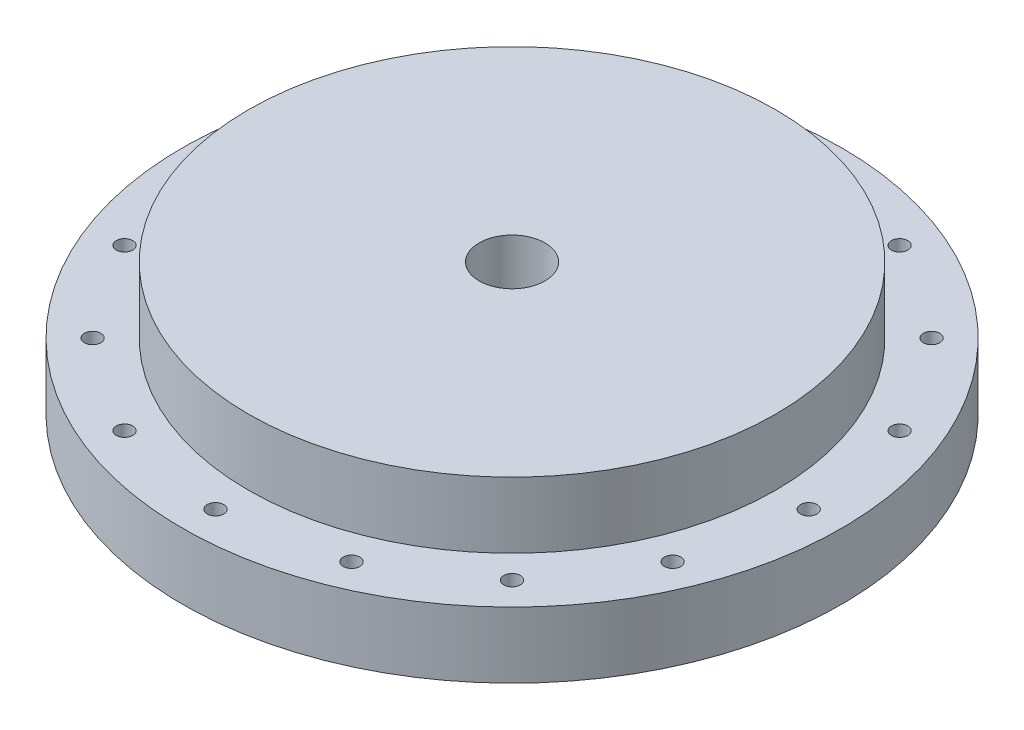
SolidWorks part; units mm, degrees
ref_plane "Front Plane" through (0, 0, 0) normal (0, 0, 1) x (1, 0, 0)
ref_plane "Top Plane" through (0, 0, 0) normal (0, 1, 0) x (1, 0, 0)
ref_plane "Right Plane" through (0, 0, 0) normal (1, 0, 0) x (0, 0, -1)
sketch "Sketch1" plane through (0, 0, 0) normal (0, 1, 0) x (1, 0, 0)
  circle A1 centre (0, 0) radius 50.8
  dimension "D1" = 101.6
extrude "Boss-Extrude1" add sketch "Sketch1" along normal blind 25.4
sketch "Sketch2" plane through (0, 0, 0) normal (0, -1, 0) x (1, 0, 0)
  circle A0 centre (0, 0) radius 50.8
  circle A1 centre (0, 0) radius 63.5
  dimension "D1" = 127
extrude "Boss-Extrude2" add sketch "Sketch2" against normal blind 12.7
sketch "Sketch3" plane through (0, 0, 0) normal (0, -1, 0) x (1, 0, 0)
  circle A0 centre (0, 0) radius 50.0062
  circle A1 centre (0, 0) radius 47.625
  dimension "D1" = 100.0125
  dimension "D2" = 95.25
extrude "Cut-Extrude1" cut sketch "Sketch3" against normal blind 1.1906
sketch "Sketch4" plane through (0, 0, 0) normal (0, -1, 0) x (1, 0, 0)
  circle A0 centre (0, -57.15) radius 1.5875
  circle A1 centre (-21.8704, -52.7997) radius 1.5875
  circle A2 centre (-40.4112, -40.4112) radius 1.5875
  circle A3 centre (-52.7997, -21.8704) radius 1.5875
  circle A4 centre (-57.15, 0) radius 1.5875
  circle A5 centre (-52.7997, 21.8704) radius 1.5875
  circle A6 centre (-40.4112, 40.4112) radius 1.5875
  circle A7 centre (-21.8704, 52.7997) radius 1.5875
  circle A8 centre (0, 57.15) radius 1.5875
  circle A9 centre (21.8704, 52.7997) radius 1.5875
  circle A10 centre (40.4112, 40.4112) radius 1.5875
  circle A11 centre (52.7997, 21.8704) radius 1.5875
  circle A12 centre (57.15, 0) radius 1.5875
  circle A13 centre (52.7997, -21.8704) radius 1.5875
  circle A14 centre (40.4112, -40.4112) radius 1.5875
  circle A15 centre (21.8704, -52.7997) radius 1.5875
  point P35 (0, 0)
  dimension "D2" = 3.175
  dimension "D1" = 57.15
  dimension "D3" = 16
extrude "Cut-Extrude2" cut sketch "Sketch4" against normal up to next
sketch "Sketch5" plane through (0, 25.4, 0) normal (0, 1, 0) x (1, 0, 0)
  circle A0 centre (0, 0) radius 6.35
  dimension "D1" = 12.7
extrude "Cut-Extrude3" cut sketch "Sketch5" against normal blind 12.7
sketch "Sketch6" plane through (0, 12.7, 0) normal (0, 1, 0) x (1, 0, 0)
  circle A0 centre (0, 0) radius 1.5875
  dimension "D1" = 3.175
extrude "Cut-Extrude4" cut sketch "Sketch6" against normal up to next
